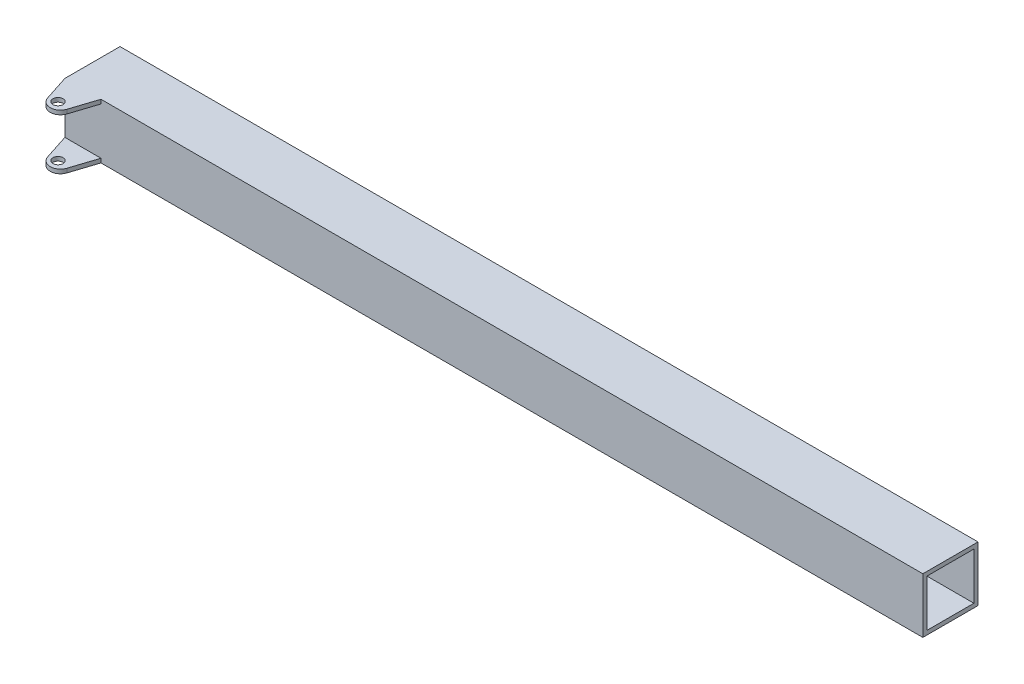
SolidWorks part; units mm, degrees
material "Plain Carbon Steel"
ref_plane "Front Plane" through (0, 0, 0) normal (0, 0, 1) x (1, 0, 0)
ref_plane "Top Plane" through (0, 0, 0) normal (0, 1, 0) x (1, 0, 0)
ref_plane "Right Plane" through (0, 0, 0) normal (1, 0, 0) x (0, 0, -1)
sketch "Sketch1" plane through (0, 0, 0) normal (1, 0, 0) x (0, 0, -1)
  line L1 (135, 270) -> (135, 0)
  line L3 (135, 0) -> (-135, 0)
  line L5 (-135, 270) -> (135, 270)
  line L6 (-135, 270) -> (-135, 0)
  line L7 (-135, 20) -> (-115, 20) construction
  line L8 (-115, 250) -> (115, 250)
  line L9 (-115, 250) -> (-115, 20)
  line L10 (-115, 20) -> (115, 20)
  line L11 (115, 250) -> (115, 20)
  line L12 (115, 250) -> (115, 270) construction
  line L13 (115, 250) -> (135, 250) construction
  line L14 (-115, 20) -> (-115, 0) construction
  dimension "D1" = 270
  dimension "D2" = 20
  dimension "D4" = 270
extrude "Boss-Extrude1" add sketch "Sketch1" against normal blind 4200
sketch "Sketch2" plane through (0, 0, 0) normal (0, -1, 0) x (1, 0, 0)
  line L0 (0, 135) -> (0, -135) construction
  circle A0 centre (-200, 0) radius 25
  dimension "D1" = 50
  dimension "D2" = 200
extrude "Boss-Extrude2" add sketch "Sketch2" against normal through all
sketch "Sketch3" plane through (0, 0, 0) normal (0, 1, 0) x (1, 0, 0)
  line L0 (-4023.2453, -135) -> (-4064.0768, -260.4725)
  line L1 (-4200, -135) -> (0, -135) construction
  line L2 (-4159.1684, -260.4725) -> (-4200, -135)
  line L3 (-4200, -135) -> (-4023.2453, -135)
  arc A1 (-4159.1684, -260.4725) -> (-4064.0768, -260.4725) centre (-4111.6226, -245) ccw
  circle A2 centre (-4118.2165, -250.297) radius 25
  point P13 (-4111.6226, -135)
  dimension "D1" = 50
  dimension "D3" = 50
  dimension "D2" = 110
extrude "Boss-Extrude3" add sketch "Sketch3" along normal blind 20
ref_plane "Plane1" through (0, 135, 0) normal (0, -1, 0) x (-1, 0, 0)
mirror "Mirror1" about plane through (0, 135, 0) normal (0, -1, 0) of "Boss-Extrude3"
